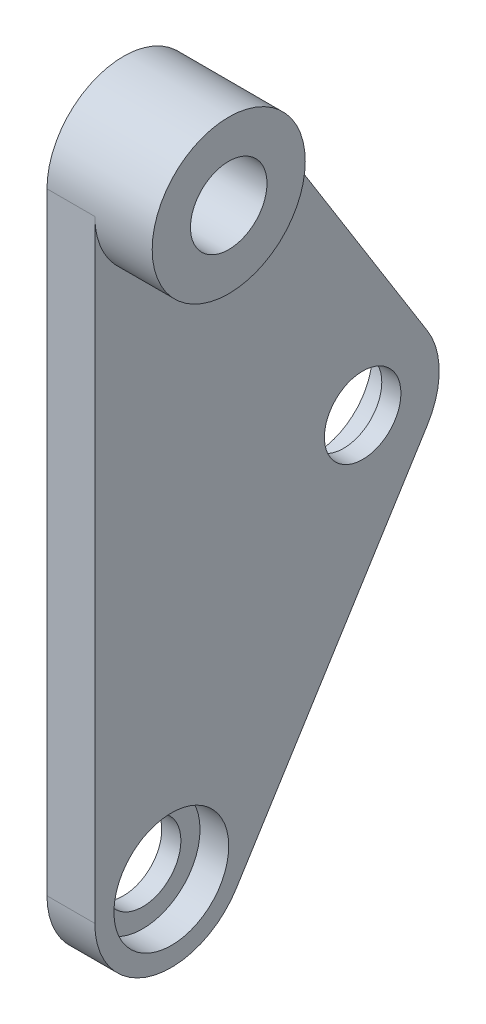
SolidWorks part; units mm, degrees
ref_plane "前视基准面" through (0, 0, 0) normal (0, 0, 1) x (1, 0, 0)
ref_plane "上视基准面" through (0, 0, 0) normal (0, 1, 0) x (1, 0, 0)
ref_plane "右视基准面" through (0, 0, 0) normal (1, 0, 0) x (0, 0, -1)
other "Configuration Table"
sketch "草图1" plane through (0, 0, 0) normal (1, 0, 0) x (0, 0, -1)
  line L0 (0, -20) -> (18, -20) construction
  line L1 (0, 0) -> (18, 0) construction
  line L2 (0, 0) -> (0, -40)
  line L3 (0, -40) -> (18, -40) construction
  line L4 (18, 0) -> (18, -40) construction
  line L5 (7.392, -1.88) -> (17.392, -17.88)
  line L6 (17.392, -22.12) -> (7.392, -38.12)
  circle A0 centre (4, -4) radius 4
  circle A1 centre (4, -36) radius 4
  circle A2 centre (14, -20) radius 4
  circle A3 centre (4, -4) radius 2
  circle A4 centre (14, -20) radius 2
  circle A5 centre (4, -36) radius 2
  dimension "D1" = 8
  dimension "D2" = 4
  dimension "D3" = 40
  dimension "D4" = 18
extrude "凸台-拉伸1" add sketch "草图1" along normal blind 2.5 contours A2 L5 A0 L2 A1 L6 | A0 | A2 | A1 region at (0, -20, -6.5849)
extrude "凸台-拉伸2" add sketch "草图1<4>" against normal blind 3 contours A0
sketch "草图1<4>" plane through (0, 0, 0) normal (1, 0, 0) x (0, 0, -1) same geometry as "草图1"
extrude "切除-拉伸1" cut sketch "草图1<3>" along normal through all both and the other way through all contours A3 | A4 | A5
sketch "草图1<3>" plane through (0, 0, 0) normal (1, 0, 0) x (0, 0, -1) same geometry as "草图1"
sketch "草图2" plane through (2.5, 0, 0) normal (1, 0, 0) x (0, 0, -1)
  circle A0 centre (4, -4) radius 3
  circle A1 centre (14, -20) radius 3
  circle A2 centre (4, -36) radius 3
  circle M3 centre (4, -4) radius 2
  arc M9 (7.392, -1.88) -> (0, -4) centre (4, -4) ccw
  dimension "D1" = 6
extrude "切除-拉伸2" cut sketch "草图2" against normal blind 1.5 contours A0 M9 M3 | A1 region at (2.5, -4, -1.0849)
extrude "切除-拉伸3" cut sketch "草图2<3>" along normal blind 1.5 from surface contours A2 starting at face at (0, -20, -16)
sketch "草图2<3>" plane through (2.5, 0, 0) normal (1, 0, 0) x (0, 0, -1) same geometry as "草图2"
ref_plane "基准面1" through (3.5, 0, 0) normal (1, 0, 0) x (0, 0, -1)
mirror "镜向2" about plane through (3.5, 0, 0) normal (1, 0, 0) of bodies 111 109
sketch "草图3" plane through (0, 0, 0) normal (0, 0, 1) x (1, 0, 0)
  line L1 (-4.5571, 5.5451) -> (3.4263, 5.5451)
  line L2 (-4.5571, 5.5451) -> (-4.5571, -46.6048)
  line L3 (-4.5571, -46.6048) -> (3.4263, -46.6048)
  line L4 (3.4263, 5.5451) -> (3.4263, -46.6048)
extrude "切除-拉伸4" cut sketch "草图3" against normal through all contours L2 L3 L4 L1
